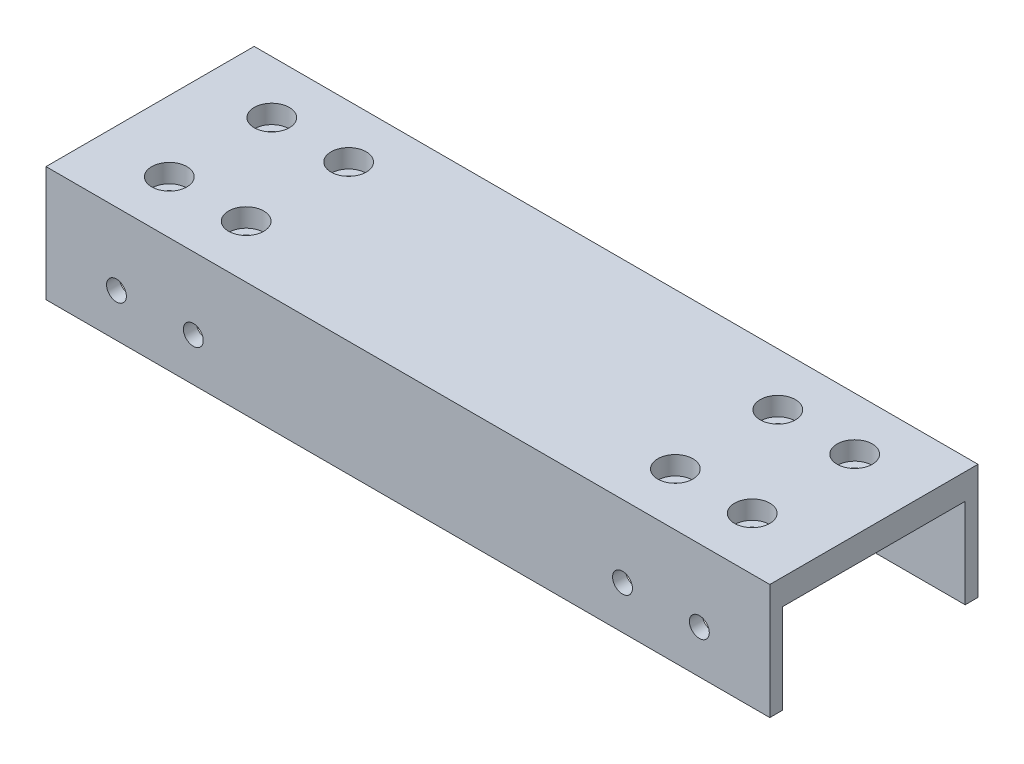
SolidWorks part; units mm, degrees
ref_plane "Front Plane" through (0, 0, 0) normal (0, 0, 1) x (1, 0, 0)
ref_plane "Top Plane" through (0, 0, 0) normal (0, 1, 0) x (1, 0, 0)
ref_plane "Right Plane" through (0, 0, 0) normal (1, 0, 0) x (0, 0, -1)
sketch "Sketch1" plane through (0, 0, 0) normal (0, 1, 0) x (1, 0, 0)
  line L1 (0, 0) -> (113, 0)
  line L2 (0, 0) -> (0, 32.5)
  line L3 (0, 32.5) -> (113, 32.5)
  line L4 (113, 0) -> (113, 32.5)
  dimension "D1" = 32.5
  dimension "D2" = 113
extrude "Boss-Extrude1" add sketch "Sketch1" along normal blind 4
sketch "Sketch4" plane through (0, 4, 0) normal (0, 1, 0) x (1, 0, 0)
  line L0 (56.5, 32.5) -> (56.5, -12.4802) construction
  line L1 (113, 32.5) -> (0, 32.5) construction
  line L3 (0, 16.25) -> (122.1673, 16.25) construction
  line L4 (0, 32.5) -> (0, 0) construction
  point P0 (11, 24.25)
  point P12 (23, 24.25)
  point P13 (23, 8.25)
  point P14 (11, 8.25)
  point P25 (102, 8.25)
  point P26 (90, 8.25)
  point P27 (90, 24.25)
  point P28 (102, 24.25)
  dimension "D1" = 2
  dimension "D3" = 12
  dimension "D4" = 16
  dimension "D5" = 8
  dimension "D6" = 79
  dimension "D2" = 2
hole_wizard "CBORE for M2.5 Hex Socket Head Cap Screw1" positions "Sketch4" profile "Sketch3" counterbore size "M2.5" standard "DIN" end condition through all
sketch "Sketch3" plane through (11, 4, -24.25) normal (1, 0, 0) x (0, 0, 1)
  line L0 (0, 0) -> (0, 4)
  line L1 (0, 4) -> (1.45, 4)
  line L3 (1.45, 4) -> (1.45, 2.9)
  line L4 (1.45, 2.9) -> (2.75, 2.9)
  line L5 (2.75, 2.9) -> (2.75, 0)
  line L7 (2.75, 0) -> (0, 0)
  line L11 (0, -6.35) -> (0, 107.95) construction
  dimension "Thru Hole Dia." = 2.9
  dimension "Thru Hole Depth" = 4
  dimension "C'Bore Dia." = 5.5
  dimension "C'Bore Depth" = 2.9
sketch "Sketch5" plane through (0, 0, 0) normal (0, -1, 0) x (1, 0, 0)
  line L0 (0, -16.25) -> (113, -16.25) construction
  line L1 (0, 0) -> (113, 0)
  line L3 (0, -32.5) -> (113, -32.5)
  line L5 (0, -2) -> (113, -2)
  line L7 (0, -30.5) -> (113, -30.5)
  line L9 (0, -16.25) -> (113, -16.25) construction
  line L20 (0, 0) -> (0, -2)
  line L23 (0, -32.5) -> (0, -30.5)
  line L24 (113, 0) -> (113, -2)
  line L25 (113, -30.5) -> (113, -32.5)
  dimension "D1" = 28.5
extrude "Boss-Extrude2" add sketch "Sketch5" along normal blind 14
sketch "Sketch7" plane through (0, -14, 0) normal (0, -1, 0) x (1, 0, 0)
  line L1 (0, -2) -> (113, -2) construction
  line L2 (34.5, -2) -> (78.5, -2)
  line L3 (34.5, -2) -> (34.5, -30.5)
  line L5 (113, -30.5) -> (0, -30.5) construction
  line L6 (34.5, -30.5) -> (78.5, -30.5)
  line L21 (78.5, -2) -> (78.5, -30.5)
  line L22 (113, -30.5) -> (0, -30.5) construction
  point P10 (56.5, -30.5)
  dimension "D1" = 44
extrude "Boss-Extrude3" add sketch "Sketch7" against normal up to next
sketch "Sketch10" plane through (0, 0, -32.5) normal (0, 0, -1) x (-1, 0, 0)
  line L1 (0, 0) -> (-34.5, 0) construction
  line L2 (-23, -7.25) -> (-11, -7.25)
  line L3 (-9.55, 1.1) -> (-12.45, 1.1) construction
  line L4 (-9.55, 1.1) -> (-12.45, 1.1)
  line L5 (-11, 1.1) -> (-11, -7.25)
  line L8 (-56.5, 4) -> (-56.5, -40.6573) construction
  line L9 (-113, 4) -> (0, 4) construction
  point P0 (-11, -7.25)
  point P2 (-23, -7.25)
  point P29 (0, 0)
  point P30 (-102, -7.25)
  point P31 (-90, -7.25)
  dimension "D1" = 7.25
  dimension "D2" = 12
hole_wizard "M2.5 Clearance Hole1" positions "Sketch10" profile "Sketch9" hole size "M2.5" standard "DIN" end condition through all
sketch "Sketch9" plane through (11, -7.25, -32.5) normal (1, 0, 0) x (0, 1, 0)
  line L0 (0, 0) -> (0, 32.5)
  line L1 (0, 32.5) -> (1.55, 32.5)
  line L2 (1.55, 32.5) -> (1.55, 0)
  line L5 (1.55, 0) -> (0, 0)
  line L11 (0, -6.35) -> (0, 107.95) construction
  dimension "Thru Hole Dia." = 3.1
  dimension "Thru Hole Depth" = 32.5
